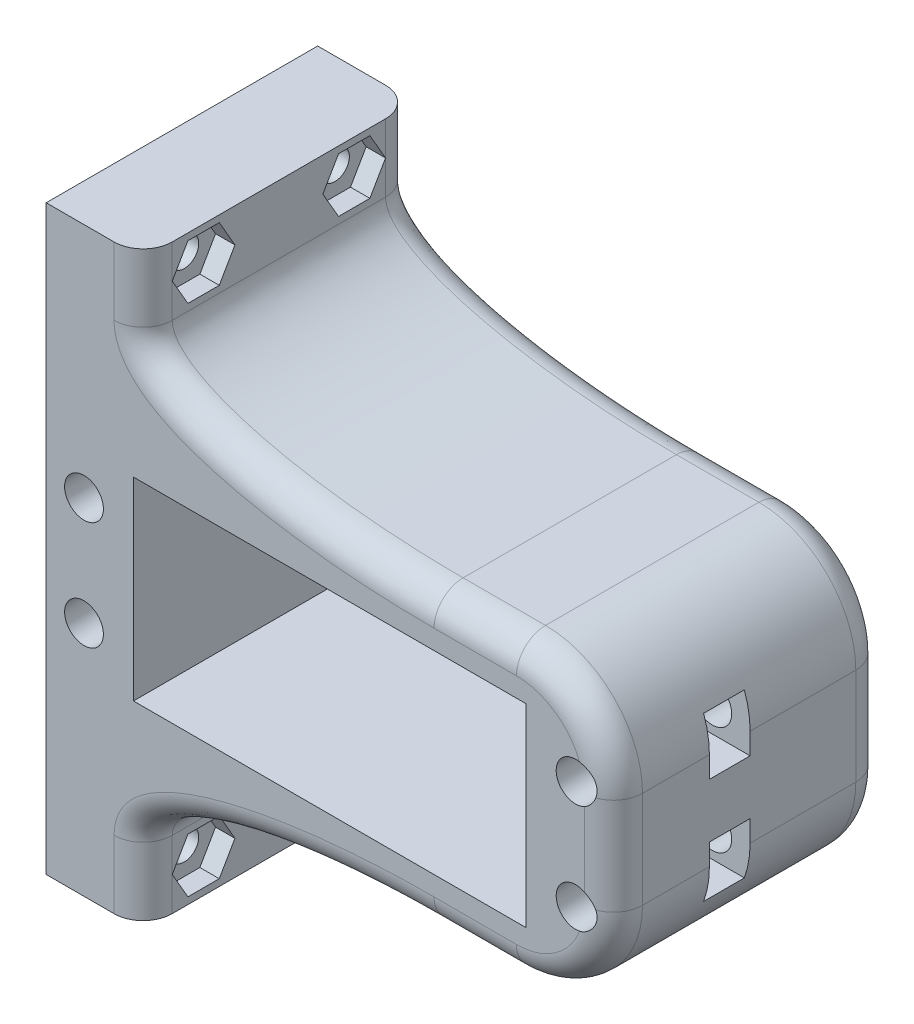
SolidWorks part; units mm, degrees
material "20% infill ABS"
ref_plane "Front" through (0, 0, 0) normal (0, 0, 1) x (1, 0, 0)
ref_plane "Top" through (0, 0, 0) normal (0, 1, 0) x (1, 0, 0)
ref_plane "Right" through (0, 0, 0) normal (1, 0, 0) x (0, 0, -1)
sketch "Sketch1" plane through (0, 0, 0) normal (0, 0, 1) x (1, 0, 0)
  line L1 (-9, -5) -> (49.5, -5)
  line L3 (-9, 25) -> (49.5, 25)
  line L4 (0, 0) -> (40.5, 0)
  line L5 (40.5, 0) -> (40.5, 20)
  line L6 (40.5, 20) -> (0, 20)
  line L7 (0, 20) -> (0, 0)
  line L8 (0, 0) -> (40.5, 0)
  line L9 (40.5, 0) -> (40.5, 20)
  line L10 (40.5, 20) -> (0, 20)
  line L11 (0, 20) -> (0, 0)
  line L12 (49.5, -5) -> (49.5, 25)
  line L13 (47.5, 3.7755) -> (47.5, 0) construction
  line L17 (-9, 25) -> (-9, -5)
  point P8 (0, 0)
  point P12 (0, 0)
  dimension "D2" = 5
  dimension "D3" = 5
  dimension "D4" = 2
  dimension "D5" = 9
  dimension "D1" = 0
extrude "Boss-Extrude1" add sketch "Sketch1" against normal up to surface (28 mm away)
ref_plane "Plane1" through (0, 0, -12) normal (0, 0, 1) x (1, 0, 0)
sketch "Sketch2" plane through (0, 0, -28) normal (0, 0, -1) x (-1, 0, 0)
  arc A0 (-47.5, 14.9755) -> (-47.5, 16.2245) centre (-45.6, 15.6) ccw construction
  arc A1 (-47.5, 3.7755) -> (-47.5, 5.0245) centre (-45.6, 4.4) ccw construction
  arc A2 (7, 16.2245) -> (7, 14.9755) centre (5.1, 15.6) ccw construction
  arc A3 (7, 5.0245) -> (7, 3.7755) centre (5.1, 4.4) ccw construction
  circle A4 centre (-45.6, 15.6) radius 2
  circle A5 centre (-45.6, 4.4) radius 2
  circle A6 centre (5.1, 15.6) radius 2
  circle A7 centre (5.1, 4.4) radius 2
  point P12 (0, 0)
  point P14 (0, 0)
  point P16 (0, 0)
  point P18 (0, 0)
extrude "Cut-Extrude1" cut sketch "Sketch2" against normal through all
sketch "Sketch3" plane through (0, 0, -12) normal (0, 0, 1) x (1, 0, 0)
  line L0 (49.5, 10) -> (-9, 10) construction
  line L7 (49.5, -5) -> (49.5, 25) construction
  line L8 (-9, 25) -> (-9, -5) construction
  line L9 (43.9834, 1.6) -> (42.3668, 4.4)
  line L10 (20.25, 20) -> (20.25, 0) construction
  line L13 (49.5, 18.4) -> (43.9834, 18.4)
  line L14 (42.3668, 4.4) -> (43.9834, 7.2)
  line L15 (43.9834, 18.4) -> (42.3668, 15.6)
  line L16 (42.3668, 15.6) -> (43.9834, 12.8)
  line L17 (43.9834, 12.8) -> (49.5, 12.8)
  line L28 (40.5, 20) -> (0, 20) construction
  line L29 (0, 0) -> (40.5, 0) construction
  line L30 (49.5, 18.4) -> (49.5, 12.8)
  line L33 (48.8332, 15.6) -> (48.0249, 17) [skipped]
  line L34 (47.2166, 12.8) -> (48.0249, 14.2) [skipped]
  line L35 (49.5, 18.4) -> (49.5, 12.8)
  line L36 (43.9834, 7.2) -> (49.5, 7.2)
  line L37 (49.5, 1.6) -> (49.5, 7.2)
  line L38 (49.5, 1.6) -> (43.9834, 1.6)
  line L39 (-1.8668, 15.6) -> (-3.4834, 12.8)
  line L40 (-3.4834, 18.4) -> (-1.8668, 15.6)
  line L41 (-9, 18.4) -> (-3.4834, 18.4)
  line L42 (-9, 18.4) -> (-9, 12.8)
  line L43 (-3.4834, 12.8) -> (-9, 12.8)
  line L44 (-3.4834, 7.2) -> (-9, 7.2)
  line L45 (-9, 1.6) -> (-9, 7.2)
  line L46 (-9, 1.6) -> (-3.4834, 1.6)
  line L47 (-3.4834, 1.6) -> (-1.8668, 4.4)
  line L48 (-1.8668, 4.4) -> (-3.4834, 7.2)
  circle A0 centre (45.6, 15.6) radius 2.8 construction
  point P1 (0, 0)
  point P2 (49.3739, 18.4)
  point P3 (0, 0)
  point P36 (0, 0)
  dimension "D1" = 5.6
extrude "Cut-Extrude4" cut sketch "Sketch3" against normal mid plane 4.2 contours L43 L39 L40 L41 L42 | L47 L48 L44 L45 L46 | L38 L37 L36 L14 L9 | L30 L13 L15 L16 L17 | L41 L40 L39 L43 L42 region at (46.3203, 4.4, -12) region at (46.3203, 15.6, -12) region at (-5.8203, 15.6, -12) region at (-5.8203, 4.4, -12)
sketch "Sketch4" plane through (-9, 0, 0) normal (-1, 0, 0) x (0, 0, 1)
  line L0 (-28, 25) -> (-28, -5) construction
  line L1 (0, 25) -> (-28, 25)
  line L2 (0, 25) -> (0, 40)
  line L3 (0, 40) -> (-28, 40)
  line L4 (-28, 25) -> (-28, 40)
  dimension "D1" = 15
extrude "Boss-Extrude2" add sketch "Sketch4" against normal blind 10
fillet "Fillet1" radius 8 1 edges at (1, 25, -14) second distance 30 first distance on face at (1, 32.5, -14)
sketch "Sketch6" plane through (1, 0, 0) normal (1, 0, 0) x (0, 0, -1)
  line L0 (28, 36.5) -> (0, 36.5) construction
  line L1 (25, 36.5) -> (23.3834, 39.3)
  line L2 (23.3834, 39.3) -> (20.1503, 39.3)
  line L3 (20.1503, 39.3) -> (18.5337, 36.5)
  line L4 (18.5337, 36.5) -> (20.1503, 33.7)
  line L5 (20.1503, 33.7) -> (23.3834, 33.7)
  line L6 (23.3834, 33.7) -> (25, 36.5)
  line L7 (28, 40) -> (28, 33) construction
  line L8 (0, 33) -> (0, 40) construction
  line L9 (14, 40) -> (14, 33) construction
  line L10 (0, 40) -> (28, 40) construction
  line L11 (0, 33) -> (28, 33) construction
  line L12 (4.6166, 33.7) -> (3, 36.5)
  line L13 (7.8497, 33.7) -> (4.6166, 33.7)
  line L14 (9.4663, 36.5) -> (7.8497, 33.7)
  line L15 (7.8497, 39.3) -> (9.4663, 36.5)
  line L16 (4.6166, 39.3) -> (7.8497, 39.3)
  line L17 (3, 36.5) -> (4.6166, 39.3)
  circle A0 centre (21.7668, 36.5) radius 1.5
  circle A1 centre (21.7668, 36.5) radius 2.8 construction
  circle A2 centre (6.2332, 36.5) radius 1.5
  dimension "D2" = 3
  dimension "D1" = 5.6
  dimension "D3" = 3
extrude "Cut-Extrude5" cut sketch "Sketch6" against normal through all contours A0 | A2
extrude "Cut-Extrude6" cut sketch "Sketch6<4>" against normal blind 2
sketch "Sketch6<4>" plane through (1, 0, 0) normal (1, 0, 0) x (0, 0, -1) same geometry as "Sketch6"
ref_plane "Plane2" through (0, 10, 0) normal (0, 1, 0) x (1, 0, 0)
mirror "Mirror2" about plane through (0, 10, 0) normal (0, 1, 0) of "Cut-Extrude5", "Cut-Extrude6", "Boss-Extrude2"
fillet "Fillet2" radius 30 1 edges at (1, -5, -14) second distance 8 first distance on face at (25.25, -5, -14)
fillet "Fillet3" radius 10 2 edges at (49.5, -5, -14) (49.5, 25, -14)
fillet "Fillet4" radius 3 9 edges at (46.5711, 22.0711, -28) (49.5, 10, -28) (46.5711, -2.0711, -28)
fillet "Fillet5" radius 3 9 edges at (46.5711, 22.0711, 0) (46.5711, -2.0711, 0) (49.5, 10, 0)
